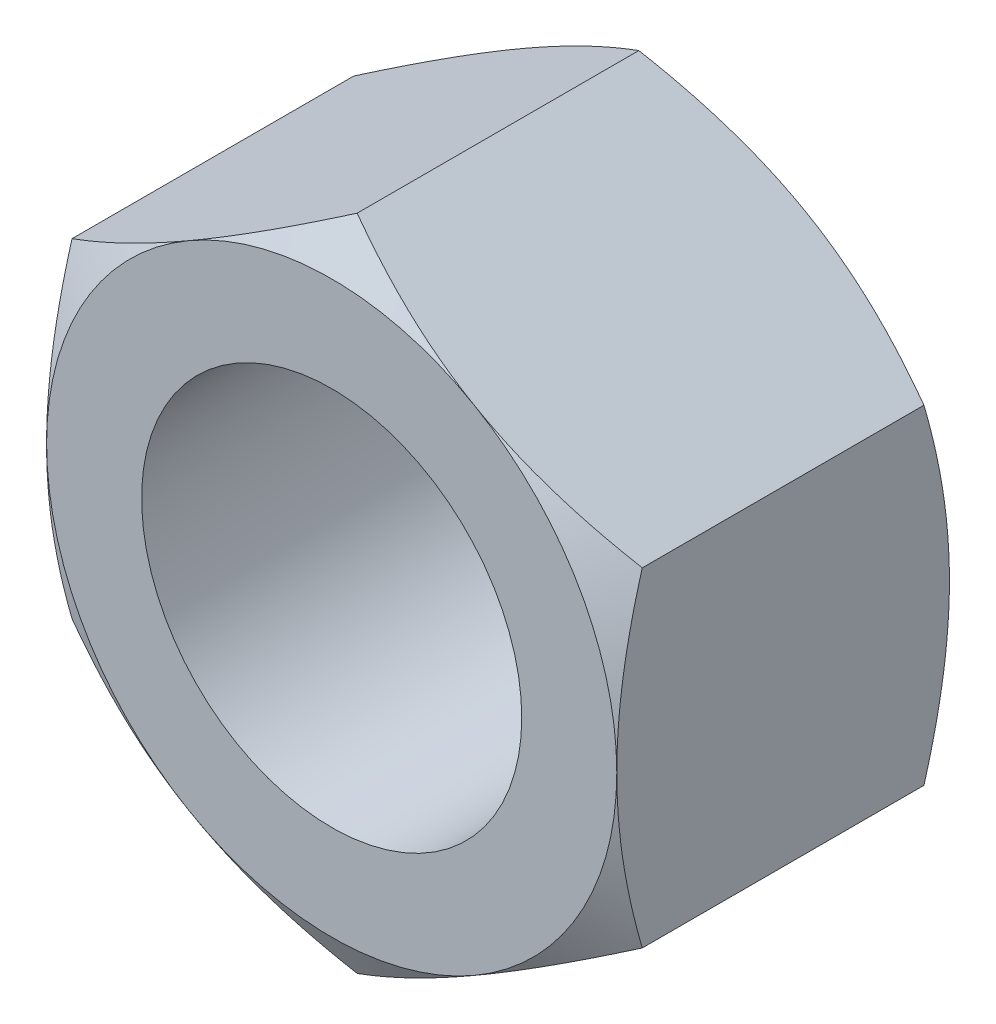
SolidWorks part; units mm, degrees
ref_plane "Front" through (0, 0, 0) normal (0, 0, 1) x (1, 0, 0)
ref_plane "Top" through (0, 0, 0) normal (0, 1, 0) x (1, 0, 0)
ref_plane "Right" through (0, 0, 0) normal (1, 0, 0) x (0, 0, -1)
sketch "Sketch1" plane through (0, 0, 0) normal (0, 0, 1) x (1, 0, 0)
  line L1 (-9.525, 5.4993) -> (-9.525, -5.4993)
  line L2 (-9.525, -5.4993) -> (0, -10.9985)
  line L3 (0, -10.9985) -> (9.525, -5.4993)
  line L4 (9.525, -5.4993) -> (9.525, 5.4993)
  line L5 (9.525, 5.4993) -> (0, 10.9985)
  line L6 (0, 10.9985) -> (-9.525, 5.4993)
  circle A0 centre (0, 0) radius 9.525 construction
  circle A1 centre (0, 0) radius 6.35
  point P10 (0, 6.35)
  dimension "hex" = 19.05
  dimension "dia" = 12.7
extrude "Extrude1" add sketch "Sketch1" along normal mid plane 11.1125
sketch "Sketch4" plane through (0, 0, -5.5562) normal (0, 0, -1) x (-1, 0, 0)
  circle A0 centre (0, 0) radius 6.35 construction
  circle A1 centre (0, 0) radius 6.35
curve "Helix/Spiral3" [suppressed] pitch 1.9538 height 13.335 turns 6.825
sketch "Sketch3" plane through (0, 0, 0) normal (1, 0, 0) x (0, 0, -1)
  line L0 (5.5562, 6.35) -> (7.2659, 6.35)
  line L1 (7.2659, 6.35) -> (6.5332, 5.0809)
  line L2 (6.5332, 5.0809) -> (6.2889, 5.0809)
  line L3 (6.2889, 5.0809) -> (5.5562, 6.35)
  line L4 (5.9226, 5.7155) -> (6.8995, 5.7155) construction
  dimension "D1" = 60
  dimension "D2" = 0.9769
  dimension "D3" = 0.2442
sweep "Sweep1" [suppressed] add profiles "Sketch3" path "Helix/Spiral3"
sketch "Sketch6" [suppressed] plane through (0, 0, 0) normal (1, 0, 0) x (0, 0, -1)
  line L0 (-6.0447, 6.8385) -> (-5.0678, 5.8615)
  line L1 (-5.0678, 5.8615) -> (-5.0678, 0) construction
  line L2 (8.2745, 0) -> (-8.2745, 0) construction
  line L3 (-5.0678, 0) -> (-7.7781, 0)
  line L4 (-7.7781, 0) -> (-7.7781, 6.8385)
  line L5 (-7.7781, 6.8385) -> (-6.0447, 6.8385)
  line L6 (-5.0678, 5.8615) -> (0.7937, 0)
  line L7 (0.7937, 0) -> (-5.0678, 0)
  line L8 (-5.5562, -5.4993) -> (-5.5562, 5.4993) construction
  point P2 (-5.5562, 6.35)
  dimension "D2" = 0.9769
  dimension "D1" = 45
revolve "Cut-Revolve1" [suppressed] cut sketch "Sketch6" angle 360 about L3
sketch "Sketch7" plane through (0, 0, 5.5562) normal (0, 0, 1) x (1, 0, 0)
  circle A0 centre (0, 0) radius 9.525 construction
  circle A1 centre (0, 0) radius 9.525
extrude "Extrude2" cut sketch "Sketch7" against normal blind 25.4 draft 60 flip side to cut
mirror "Mirror1" about plane through (0, 0, 0) normal (0, 0, 1) of "Extrude2", "Cut-Revolve1"
sketch "Sketch8" [suppressed] plane through (0, 0, 5.5562) normal (0, 0, 1) x (1, 0, 0)
  line L0 (-4.4901, 4.4901) -> (0, 0) construction
  line L1 (0, -8.2745) -> (0, 8.2745) construction
  circle A0 centre (0, 0) radius 6.35 construction
  point P0 (-4.4901, 4.4901)
  dimension "D1" = 45
equation "\"D3@Helix/Spiral3\" = \"length@Extrude1\" * 1.2"
equation "\"D2@Sketch3\" = \"D4@Helix/Spiral3\" * .5"
equation "\"D3@Sketch3\" = \"D4@Helix/Spiral3\" * .125"
equation "\"D2@Sketch6\" = \"D4@Helix/Spiral3\" * .5"
